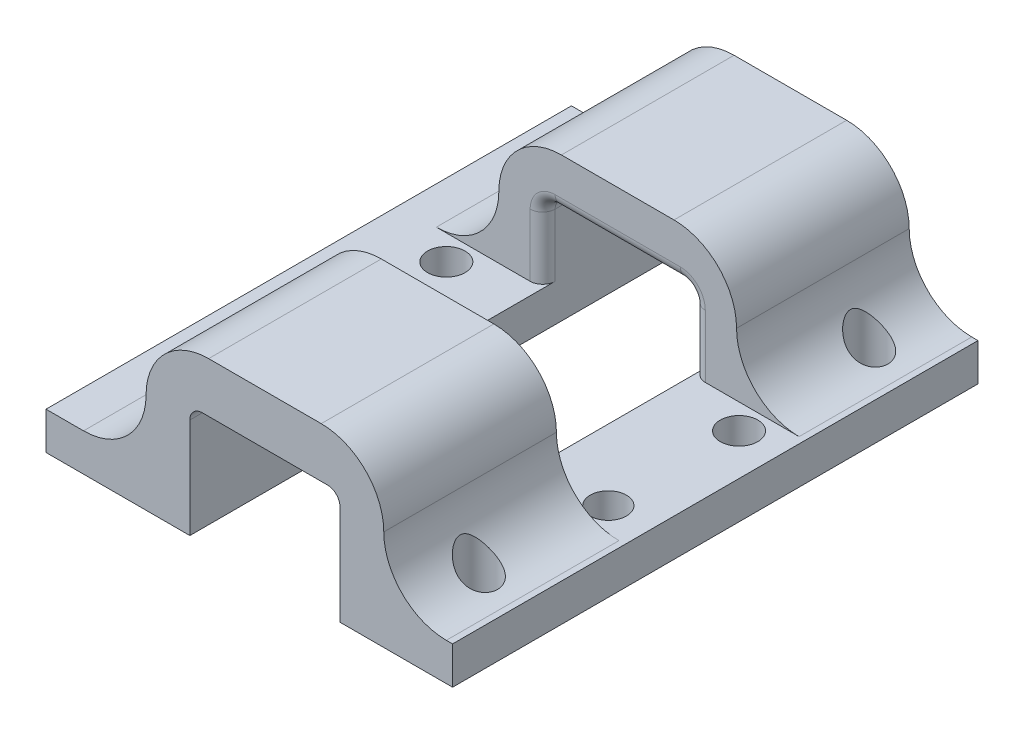
SolidWorks part; units mm, degrees
ref_plane "Спереди" through (0, 0, 0) normal (0, 0, 1) x (1, 0, 0)
ref_plane "Сверху" through (0, 0, 0) normal (0, 1, 0) x (1, 0, 0)
ref_plane "Справа" through (0, 0, 0) normal (1, 0, 0) x (0, 0, -1)
sketch "Эскиз2" plane through (0, 0, 0) normal (0, 1, 0) x (1, 0, 0)
  line L0 (-16.25, -21) -> (16.25, -21)
  line L1 (-16.25, -21) -> (-16.25, 21)
  line L2 (-16.25, 21) -> (16.25, 21)
  line L3 (16.25, -21) -> (16.25, 21)
  circle A0 centre (-10.45, -15.6) radius 1.5
  circle A1 centre (-10.45, -5.2) radius 1.5
  circle A2 centre (-10.45, 5.2) radius 1.5
  circle A3 centre (-10.45, 15.6) radius 1.5
  circle A4 centre (12.95, 15.6) radius 1.5
  circle A5 centre (12.95, 5.2) radius 1.5
  circle A6 centre (12.8998, -5.2) radius 1.4498
  circle A7 centre (12.95, -15.6) radius 1.5
extrude "Бобышка-Вытянуть1" add sketch "Эскиз2" along normal blind 3
sketch "Эскиз4" plane through (0, 3, 0) normal (0, 1, 0) x (1, 0, 0)
  line L0 (-10.45, 15.6) -> (12.95, 15.6) construction
  line L1 (1.25, 15.6) -> (1.25, -15.6) construction
  line L3 (-10.45, -15.6) -> (12.95, -15.6) construction
  line L4 (-16.25, -21) -> (16.25, -21) construction
  line L5 (-4.75, 21) -> (7.25, 21)
  line L6 (-4.75, 21) -> (-4.75, -21)
  line L7 (-4.75, -21) -> (7.25, -21)
  line L8 (7.25, 21) -> (7.25, -21)
  line L9 (-4.75, 21) -> (7.25, -21) construction
  line L10 (-4.75, -21) -> (7.25, 21) construction
  circle A0 centre (12.95, -15.6) radius 1.5 construction
  point P5 (1.25, 0)
  point P16 (11.45, -15.6)
  dimension "D1" = 12
extrude "Вырез-Вытянуть1" cut sketch "Эскиз4" against normal blind 22 contours L6 L5 L8 L7
sketch "Эскиз5" plane through (0, 0, 21) normal (0, 0, 1) x (1, 0, 0)
  line L0 (-16.25, 0) -> (-4.75, 0) construction
  line L2 (-4.75, 0) -> (-4.75, 3)
  line L4 (7.25, 0) -> (7.25, 3)
  line L6 (-4.75, 3) -> (-4.75, 9)
  line L7 (-4.75, 9) -> (7.25, 9)
  line L8 (7.25, 3) -> (7.25, 9)
  line L9 (-8.25, 0) -> (-4.75, 0)
  line L10 (-8.25, 0) -> (-8.25, 13)
  line L11 (-8.25, 13) -> (10.75, 13)
  line L12 (10.75, 0) -> (10.75, 13)
  line L13 (7.25, 0) -> (10.75, 0)
  dimension "D2" = 3.5
  dimension "D3" = 3.5
  dimension "D4" = 4
extrude "Бобышка-Вытянуть2" add sketch "Эскиз5" against normal up to surface (42 mm away) up to face at (11.75, 1.5, -21)
fillet "Скругление1" radius 5 4 edges at (-8.25, 13, 0) (10.75, 13, 0) (-8.25, 3, 0) (10.75, 3, 0)
sketch "Эскиз6" plane through (0, 13, 0) normal (0, 1, 0) x (1, 0, 0)
  line L0 (-3.25, 0) -> (5.75, 0) construction
  line L1 (-3.25, 21) -> (-3.25, -21) construction
  line L2 (5.75, -21) -> (5.75, 21) construction
  line L4 (-18.2884, -7.2) -> (18.2884, -7.2)
  line L5 (-18.2884, -7.2) -> (-18.2884, 7.2)
  line L6 (-18.2884, 7.2) -> (18.2884, 7.2)
  line L7 (18.2884, -7.2) -> (18.2884, 7.2)
  line L8 (-18.2884, -7.2) -> (18.2884, 7.2) construction
  line L9 (-18.2884, 7.2) -> (18.2884, -7.2) construction
  circle A0 centre (12.8998, -5.2) radius 1.4498 construction
  point P6 (0, 0)
  dimension "D1" = 2
extrude "Вырез-Вытянуть2" cut sketch "Эскиз6" against normal up to surface (10 mm away) up to face at (16, 3, 0)
fillet "Скругление2" radius 1 10 edges at (7.25, 6, 7.2) (7.25, 6, -7.2) (1.25, 9, 7.2) (1.25, 9, -7.2) (-4.75, 6, 7.2) (-4.75, 6, -7.2) (-4.75, 9, -14.1) (7.25, 9, -14.1) (7.25, 9, 14.1) (-4.75, 9, 14.1)
